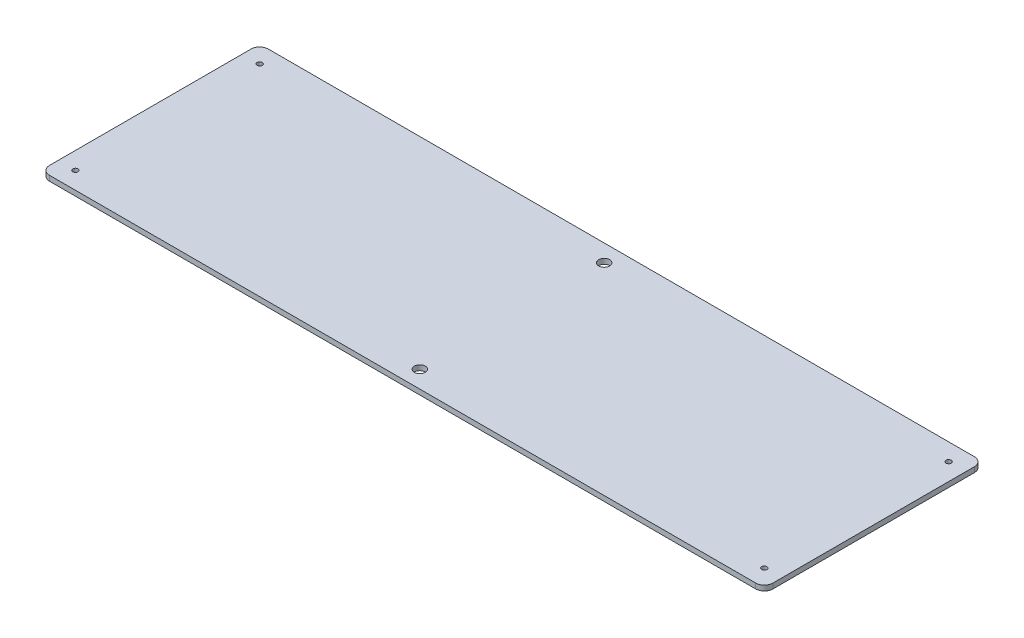
SolidWorks part; units mm, degrees
material "Thornel Mat VMA"
ref_plane "Front Plane" through (0, 0, 0) normal (0, 0, 1) x (1, 0, 0)
ref_plane "Top Plane" through (0, 0, 0) normal (0, 1, 0) x (1, 0, 0)
ref_plane "Right Plane" through (0, 0, 0) normal (1, 0, 0) x (0, 0, -1)
sketch "Sketch1" plane through (0, 0, 0) normal (0, 1, 0) x (1, 0, 0)
  line L1 (-210, 63.5) -> (210, 63.5)
  line L2 (-210, 63.5) -> (-210, -63.5)
  line L3 (-210, -63.5) -> (210, -63.5)
  line L4 (210, 63.5) -> (210, -63.5)
  line L5 (-210, 63.5) -> (210, -63.5) construction
  line L6 (-210, -63.5) -> (210, 63.5) construction
  point P0 (0, 0)
  dimension "D1" = 127
  dimension "D2" = 420
extrude "Boss-Extrude1" add sketch "Sketch1" along normal blind 3
fillet "Fillet1" radius 5 4 edges at (-210, 1.5, -63.5) (210, 1.5, -63.5) (210, 1.5, 63.5) (-210, 1.5, 63.5)
sketch "Sketch2" plane through (0, 3, 0) normal (0, 1, 0) x (1, 0, 0)
  line L0 (-205, -63.5) -> (205, -63.5) construction
  line L1 (210, -58.5) -> (210, 58.5) construction
  line L2 (205, 63.5) -> (-205, 63.5) construction
  line L3 (-210, 58.5) -> (-210, -58.5) construction
  circle A0 centre (200, -53.5) radius 1.5
  circle A1 centre (-200, -53.5) radius 1.5
  circle A2 centre (-200, 53.5) radius 1.5
  circle A3 centre (200, 53.5) radius 1.5
  dimension "D1" = 3
  dimension "D2" = 10
  dimension "D3" = 10
  dimension "D4" = 3
  dimension "D5" = 10
  dimension "D6" = 10
  dimension "D7" = 3
  dimension "D8" = 10
  dimension "D9" = 10
  dimension "D10" = 3
  dimension "D11" = 10
  dimension "D12" = 10
extrude "Cut-Extrude1" cut sketch "Sketch2" against normal blind 3
sketch "Sketch4" plane through (0, 3, 0) normal (0, 1, 0) x (1, 0, 0)
  line L0 (205, 63.5) -> (-205, 63.5) construction
  line L1 (-205, -63.5) -> (205, -63.5) construction
  circle A0 centre (0, 53.5) radius 3.175
  circle A1 centre (0, -53.5) radius 3.175
  point P6 (0, 63.5)
  dimension "D1" = 6.35
  dimension "D2" = 10
  dimension "D3" = 6.35
  dimension "D4" = 10
extrude "Cut-Extrude3" cut sketch "Sketch4" against normal blind 10
